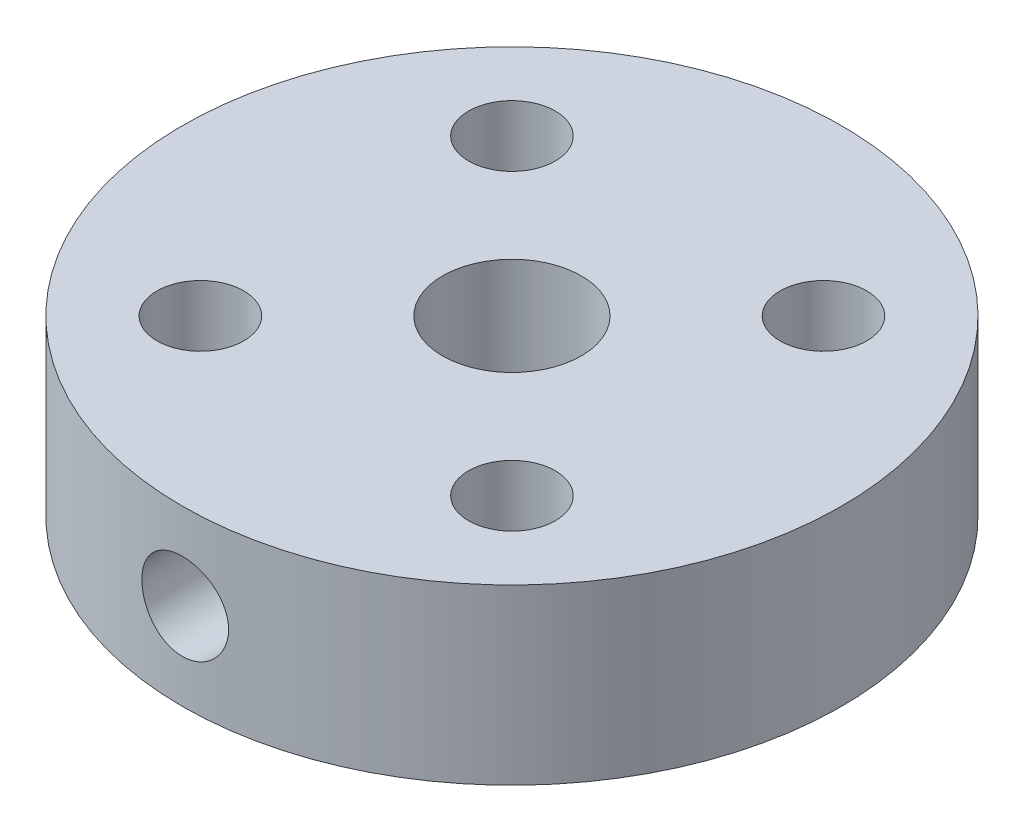
SolidWorks part; units mm, degrees
ref_plane "Front Plane" through (0, 0, 0) normal (0, 0, 1) x (1, 0, 0)
ref_plane "Top Plane" through (0, 0, 0) normal (0, 1, 0) x (1, 0, 0)
ref_plane "Right Plane" through (0, 0, 0) normal (1, 0, 0) x (0, 0, -1)
sketch "Sketch1" plane through (0, 0, 0) normal (0, 1, 0) x (1, 0, 0)
  line L0 (-9.5, 0) -> (9.5, 0) construction
  line L1 (0, 9.5) -> (0, -9.5) construction
  line L2 (0, 0) -> (6.7175, 6.7175) construction
  circle A0 centre (0, 0) radius 9.5
  circle A1 centre (0, 0) radius 2
  circle A2 centre (4.4901, 4.4901) radius 1.25
  circle A3 centre (-4.4901, 4.4901) radius 1.25
  circle A4 centre (4.4901, -4.4901) radius 1.25
  circle A5 centre (-4.4901, -4.4901) radius 1.25
  dimension "D1" = 19
  dimension "D2" = 4
  dimension "D3" = 2.5
  dimension "D4" = 6.35
  dimension "D5" = 45
extrude "Boss-Extrude1" add sketch "Sketch1" along normal blind 5
ref_plane "Plane2" through (0, 0, 9.5) normal (0, 0, 1) x (1, 0, 0)
sketch "Sketch3" plane through (0, 0, 9.5) normal (0, 0, 1) x (1, 0, 0)
  line L0 (-9.5, 2.5) -> (9.5, 2.5) construction
  line L1 (-9.5, 5) -> (-9.5, 0) construction
  line L2 (9.5, 0) -> (9.5, 5) construction
  circle A0 centre (0, 2.5) radius 1.25
  dimension "D1" = 2.5
extrude "Cut-Extrude1" cut sketch "Sketch3" against normal up to next
